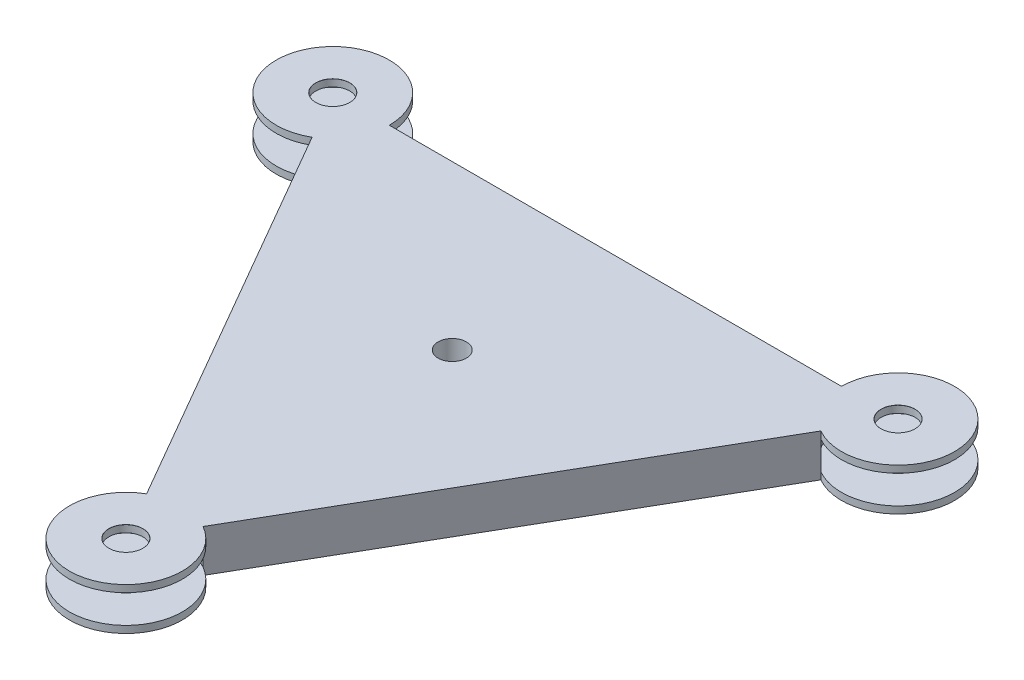
SolidWorks part; units mm, degrees
ref_plane "Plan de face" through (0, 0, 0) normal (0, 0, 1) x (1, 0, 0)
ref_plane "Plan de dessus" through (0, 0, 0) normal (0, 1, 0) x (1, 0, 0)
ref_plane "Plan de droite" through (0, 0, 0) normal (1, 0, 0) x (0, 0, -1)
sketch "Esquisse1" plane through (0, 0, 0) normal (0, 1, 0) x (1, 0, 0)
  line L3 (50, -28.8675) -> (-100, 57.735) construction
  line L6 (-50, -28.8675) -> (100, 57.735) construction
  line L16 (100, 57.735) -> (0, -115.4701)
  line L17 (0, -115.4701) -> (-100, 57.735)
  line L19 (-100, 57.735) -> (100, 57.735)
  circle A6 centre (0, 0) radius 5
  circle A7 centre (100, 57.735) radius 20
  circle A9 centre (0, -115.4701) radius 20
  circle A10 centre (-100, 57.735) radius 20
  point P11 (0, 0)
  point P12 (5.3523, 54.348)
  point P36 (0, 50)
  point P38 (0, 50)
  point P40 (0, 50)
  point P41 (0, 50)
  dimension "D2" = 5.3523
  dimension "D3" = 200
  dimension "D5" = 40
  dimension "D1" = 200
  dimension "D6" = 40
  dimension "D8" = 10
  dimension "D7" = 40
  dimension "D4" = 200
extrude "Boss.-Extru.1" add sketch "Esquisse1" along normal mid plane 15 contours A10 L17 A9 L16 A7 L19 A6 | L19 A10 L17 | L16 A7 L19 | L19 A7 L16 | L17 A10 L19 | L17 A9 L16 | L16 A9 L17 region at (102.2053, 0, -59.0083) region at (88.9734, 0, -51.3688) region at (47.9378, 0, 27.6769) region at (0, 0, 118.0165) region at (0, 0, 102.7377) region at (-88.9734, 0, -51.3688) region at (-102.2053, 0, -59.0083)
sketch "Esquisse7" plane through (0, 0, 0) normal (0, 1, 0) x (1, 0, 0)
  arc A0 (-10, -98.1495) -> (10, -98.1495) centre (0, -115.4701) ccw construction
  circle A2 centre (0, -115.4701) radius 20
  arc A4 (-80, 57.735) -> (-90, 40.4145) centre (-100, 57.735) ccw construction
  arc A6 (90, 40.4145) -> (80, 57.735) centre (100, 57.735) ccw construction
  circle A7 centre (100, 57.735) radius 20
  circle A8 centre (-100, 57.735) radius 20
extrude "Enlèv. mat.-Extru.1" cut sketch "Esquisse7" against normal mid plane 10
sketch "Esquisse14" plane through (0, 7.5, 0) normal (0, 1, 0) x (1, 0, 0)
  arc A0 (-80, 57.735) -> (-90, 40.4145) centre (-100, 57.735) ccw construction
  arc A2 (-10, -98.1495) -> (10, -98.1495) centre (0, -115.4701) ccw construction
  arc A3 (90, 40.4145) -> (80, 57.735) centre (100, 57.735) ccw construction
  point P17 (-100, 57.735)
  point P21 (100, 57.735)
  point P24 (0, -115.4701)
sketch "Esquisse18" plane through (0, 7.5, 0) normal (0, 1, 0) x (1, 0, 0)
  point P0 (-100, 57.735)
  point P3 (100, 57.735)
  point P6 (0, -115.4701)
hole_wizard "Dégagement M102" positions "Esquisse18" profile "Esquisse17" hole size "M10" standard "ISO" end condition through all
sketch "Esquisse17" plane through (-100, 7.5, -57.735) normal (1, 0, 0) x (0, 0, 1)
  line L0 (0, 0) -> (0, 15)
  line L1 (0, 15) -> (6, 15)
  line L2 (6, 15) -> (6, 0.025)
  line L3 (6, 0.025) -> (6.025, 0)
  line L5 (6.025, 0) -> (0, 0)
  line L6 (-6, 0.025) -> (-6.025, 0) construction
  line L11 (0, -6.35) -> (0, 107.95) construction
  dimension "Diamètre du perçage jusqu'au prochain" = 12
  dimension "Profondeur du perçage jusqu'au prochain" = 15
  dimension "Diamètre du fraisage entrant" = 12.05
  dimension "Angle du fraisage entrant" = 90
